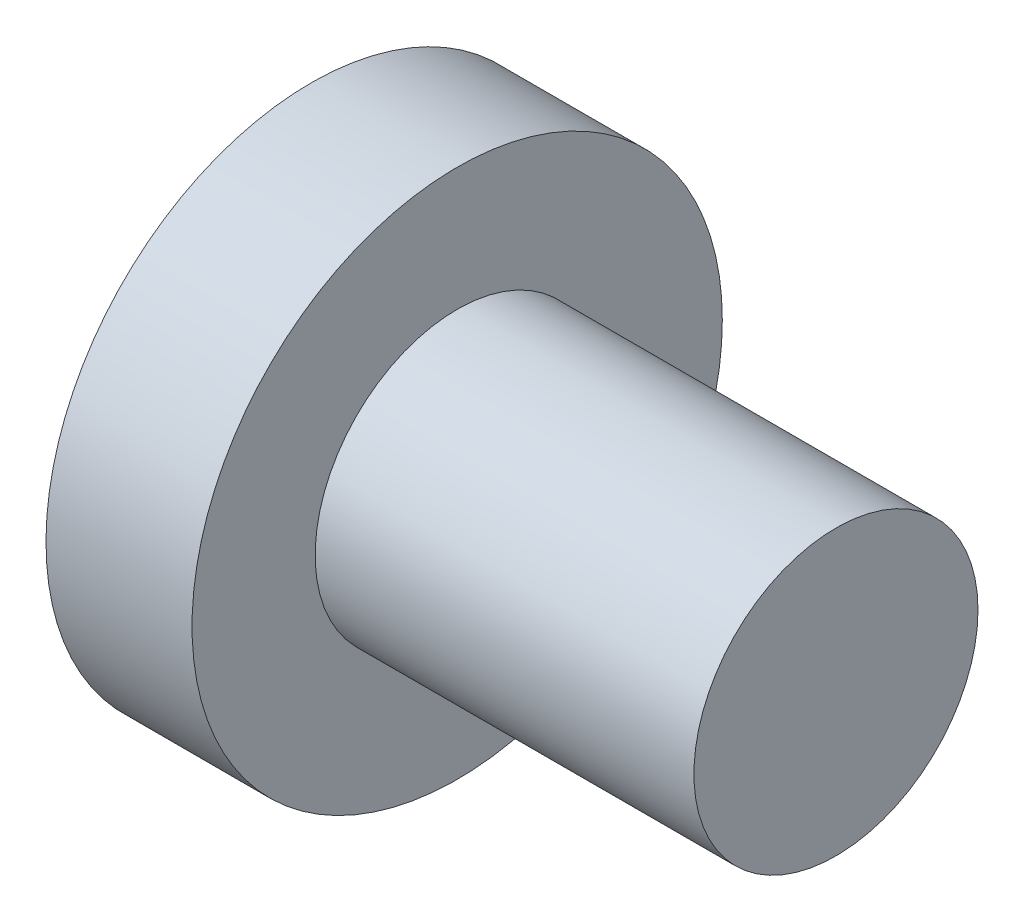
SolidWorks part; units mm, degrees
ref_plane "Front" through (0, 0, 0) normal (0, 0, 1) x (1, 0, 0)
ref_plane "Top" through (0, 0, 0) normal (0, 1, 0) x (1, 0, 0)
ref_plane "Right" through (0, 0, 0) normal (1, 0, 0) x (0, 0, -1)
sketch "Sketch1" plane through (0, 0, 0) normal (0, 0, 1) x (1, 0, 0)
  line L0 (6.4, 1.5) -> (3.4, 1.5)
  line L1 (2.4, 1.8) -> (2.4, 2.8)
  line L2 (2.4, 2.8) -> (0.8575, 2.8)
  line L3 (3.4, 1.5) -> (2.7, 1.5) construction
  line L4 (6.4, 1.5) -> (6.4, 0)
  line L5 (4.5158, 0) -> (-13.5157, 0) construction
  line L6 (6.4, 0) -> (0, 0)
  line L7 (3.4, 1.5) -> (2.4, 1.5)
  line L8 (2.4, 1.5) -> (2.4, 1.8)
  arc A0 (0.8575, 2.8) -> (0, 0) centre (5, 0) ccw
  arc A1 (2.4, 1.8) -> (2.7, 1.5) centre (2.7, 1.8) ccw construction
  dimension "r" = 0.3
  dimension "r1" = 5
  dimension "d" = 3
  dimension "dk" = 5.6
  dimension "l" = 4
  dimension "k" = 2.4
  dimension "a" = 1
  dimension "da" = 3.6
revolve "Base" add sketch "Sketch1" angle 360 about L5
cosmetic thread "ThreadCosmetic1" [suppressed] parameters "bb"=4, "THD_MINOR"=2.459
sketch "Sketch6" plane through (0, 0, 0) normal (1, 0, 0) x (0, 0, -1)
  line L0 (-1.9271, 0) -> (2.0512, 0) construction
  line L1 (0, 1.8651) -> (0, -2.0207) construction
  line L2 (0.3, 0.3) -> (0.3, 1.5)
  line L3 (0.3, 1.5) -> (-0.3, 1.5)
  line L4 (-0.3, 0.3) -> (-0.3, 1.5)
  line L5 (0.3, 0.3) -> (1.5, 0.3)
  line L6 (1.5, 0.3) -> (1.5, -0.3)
  line L7 (-1.5, 0.3) -> (-1.5, -0.3)
  line L8 (-0.3, 0.3) -> (-1.5, 0.3)
  line L9 (-0.3, -0.3) -> (-1.5, -0.3)
  line L10 (0.3, -0.3) -> (1.5, -0.3)
  line L11 (-0.3, -0.3) -> (-0.3, -1.5)
  line L12 (0.3, -1.5) -> (-0.3, -1.5)
  line L13 (0.3, -0.3) -> (0.3, -1.5)
  point P16 (-1.5, 0)
  point P17 (1.5, 0)
  dimension "D1" = 0.6
  dimension "m" = 3
extrude "CrossRecess" cut sketch "Sketch6" along normal blind 1.68
fillet "Fillet5" radius 0.3 4 edges at (0.849, -0.3, 0.3) (0.849, -0.3, -0.3) (0.849, 0.3, 0.3) (0.849, 0.3, -0.3)
draft "Draft1" type of draft neutral plane draft angle 30 neutral plane "Right" faces to draft 4 face at (0.9575, -1.5, 0) face at (0.9575, 0, -1.5) face at (0.9575, 0, 1.5) face at (0.9575, 1.5, 0) neutral plane through (0, 0, 0) neutral plane normal (1, 0, 0) reverse direction yes parameters "D1"=30
sketch "Sketch7" plane through (0, 0, 0) normal (1, 0, 0) x (0, 0, -1)
  line L0 (-2.0126, 0) -> (1.9757, 0) construction
  line L1 (0, 1.9314) -> (0, -2.0126) construction
  line L2 (0, 0) -> (1.5555, 1.5555) construction
  line L3 (0, 0.4483) -> (1.0607, 1.0607)
  line L4 (-1.5402, 1.5402) -> (0, 0) construction
  line L5 (0.4483, 0) -> (1.0607, 1.0607)
  line L6 (0, -0.4483) -> (1.0607, -1.0607)
  line L7 (0.4483, 0) -> (1.0607, -1.0607)
  line L8 (-0.4483, 0) -> (-1.0607, -1.0607)
  line L9 (0, -0.4483) -> (-1.0607, -1.0607)
  line L10 (-0.4483, 0) -> (-1.0607, 1.0607)
  line L11 (0, 0.4483) -> (-1.0607, 1.0607)
  dimension "D3" = 15
extrude "Cut-Extrude3" [suppressed] cut sketch "Sketch7" along normal blind 40.2 draft 9
sketch "Sketch8" plane through (0, 0, 0) normal (0, 0, 1) x (1, 0, 0)
  line L0 (-18.6, 1.5) -> (-19.85, 1.2295)
  line L1 (-19.85, 1.2295) -> (2.4, 1.2295)
  line L2 (6.4, -1.5) -> (6.4, 1.5) construction
  line L3 (2.4, -2.8) -> (2.4, 2.8) construction
  line L6 (2.4, 1.2295) -> (2.4, 2.8)
  line L7 (2.4, 2.8) -> (-18.6, 2.8)
  line L8 (-18.6, 2.8) -> (-18.6, 1.5)
  line L9 (73.4853, 0) -> (63.9694, 0) construction
  dimension "x" = 1.25
  dimension "b" = 25
sketch "Sketch9" plane through (0, 0, 0) normal (0, 0, 1) x (1, 0, 0)
  line L0 (6.4, 1.2657) -> (6.5352, 1.5)
  line L1 (6.5352, 1.5) -> (6.5352, 1.7705)
  line L2 (6.5352, 1.7705) -> (6.2647, 1.7705)
  line L3 (6.2647, 1.7705) -> (6.2647, 1.5)
  line L4 (6.2647, 1.5) -> (6.4, 1.2657)
  line L5 (6.4, -1.5) -> (6.4, 1.5) construction
  line L6 (0, 0) -> (76.7811, 0) construction
  dimension "D1" = 3
  dimension "D2" = 0.2705
revolve "Cut-Revolve10" [suppressed] cut sketch "Sketch9" angle 360 about L6
pattern_linear "LPattern10" [suppressed] count 12 spacing 0.3246 along (-1, 0, 0) of bodies 105
equation "\"D1@Sketch6\" = \"m@Sketch6\" / 5"
equation "\"D1@CrossRecess\" = 0.7*\"k@Sketch1\""
equation "\"D1@Sketch9\" = \"d@Sketch1\" "
equation "\"D2@Sketch9\" =  ( \"d@Sketch1\" - \"THD_MINOR@ThreadCosmetic1\" )  / 2"
equation "\"D3@LPattern10\" =\"D2@Sketch9\" * 1.2"
equation "\"D1@LPattern10\" = \"bb@ThreadCosmetic1\" / \"D3@LPattern10\" "
